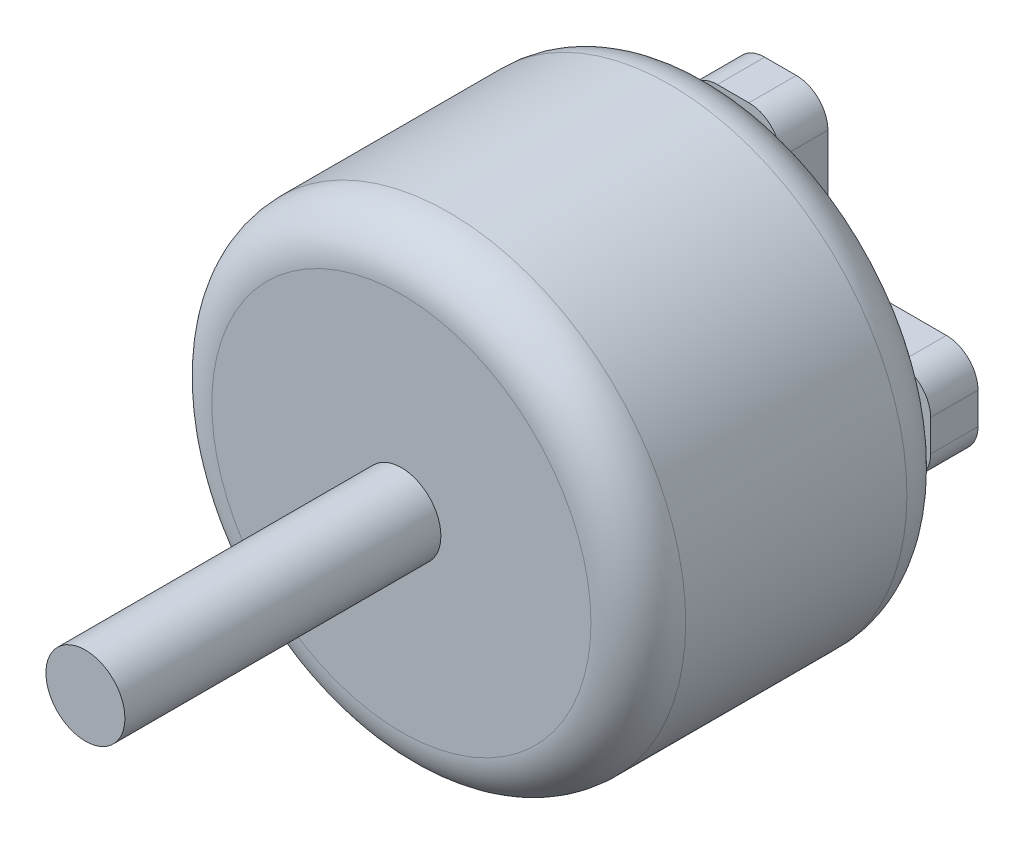
SolidWorks part; units mm, degrees
ref_plane "Front Plane" through (0, 0, 0) normal (0, 0, 1) x (1, 0, 0)
ref_plane "Top Plane" through (0, 0, 0) normal (0, 1, 0) x (1, 0, 0)
ref_plane "Right Plane" through (0, 0, 0) normal (1, 0, 0) x (0, 0, -1)
sketch "Sketch1" plane through (0, 0, 0) normal (0, 0, 1) x (1, 0, 0)
  line L0 (-71.7817, -74.7817) -> (-67.2817, -74.7817)
  line L1 (-78.7817, -65.2817) -> (-76.7817, -65.2817)
  line L2 (-80.7817, -67.2817) -> (-80.7817, -71.7817)
  line L3 (-78.7817, -90.2817) -> (-76.7817, -90.2817)
  line L4 (-74.7817, -67.2817) -> (-74.7817, -71.7817)
  line L5 (-88.2817, -74.7817) -> (-83.7817, -74.7817)
  line L6 (-90.2817, -76.7817) -> (-90.2817, -78.7817)
  line L7 (-88.2817, -80.7817) -> (-83.7817, -80.7817)
  line L8 (-65.2817, -76.7817) -> (-65.2817, -78.7817)
  line L9 (-80.7817, -83.7817) -> (-80.7817, -88.2817)
  line L10 (-74.7817, -83.7817) -> (-74.7817, -88.2817)
  line L11 (-71.7817, -80.7817) -> (-67.2817, -80.7817)
  circle A0 centre (-87.2817, -77.7817) radius 1.6 construction
  circle A1 centre (-77.7817, -87.2817) radius 1.6 construction
  circle A2 centre (-77.7817, -68.2817) radius 1.6 construction
  circle A3 centre (-68.2817, -77.7817) radius 1.6 construction
  arc A4 (-80.7817, -83.7817) -> (-83.7817, -80.7817) centre (-83.7817, -83.7817) ccw
  arc A5 (-74.7817, -83.7817) -> (-71.7817, -80.7817) centre (-71.7817, -83.7817) cw
  arc A6 (-71.7817, -74.7817) -> (-74.7817, -71.7817) centre (-71.7817, -71.7817) cw
  arc A7 (-83.7817, -74.7817) -> (-80.7817, -71.7817) centre (-83.7817, -71.7817) ccw
  arc A8 (-78.7817, -65.2817) -> (-80.7817, -67.2817) centre (-78.7817, -67.2817) ccw
  arc A9 (-76.7817, -65.2817) -> (-74.7817, -67.2817) centre (-76.7817, -67.2817) cw
  arc A10 (-67.2817, -74.7817) -> (-65.2817, -76.7817) centre (-67.2817, -76.7817) cw
  arc A11 (-67.2817, -80.7817) -> (-65.2817, -78.7817) centre (-67.2817, -78.7817) ccw
  arc A12 (-76.7817, -90.2817) -> (-74.7817, -88.2817) centre (-76.7817, -88.2817) ccw
  arc A13 (-80.7817, -88.2817) -> (-78.7817, -90.2817) centre (-78.7817, -88.2817) ccw
  arc A14 (-90.2817, -78.7817) -> (-88.2817, -80.7817) centre (-88.2817, -78.7817) ccw
  arc A15 (-88.2817, -74.7817) -> (-90.2817, -76.7817) centre (-88.2817, -76.7817) ccw
  circle A16 centre (-77.7817, -68.2817) radius 1.6
  circle A17 centre (-68.2817, -77.7817) radius 1.6
  circle A18 centre (-77.7817, -87.2817) radius 1.6
  circle A19 centre (-87.2817, -77.7817) radius 1.6
  point P24 (-74.7817, -80.7817)
  point P39 (-74.7817, -90.2817)
  point P42 (-80.7817, -90.2817)
  point P45 (-90.2817, -80.7817)
  point P48 (-90.2817, -74.7817)
  dimension "D1" = 3
  dimension "D9" = 3
  dimension "D10" = 2
  dimension "D2" = 6
  dimension "D3" = 6
  dimension "D4" = 3
  dimension "D5" = 3
  dimension "D6" = 3
  dimension "D7" = 3
  dimension "D8" = 3
extrude "Boss-Extrude1" add sketch "Sketch1" along normal blind 3
sketch "Sketch2" plane through (0, 0, 3) normal (0, 0, 1) x (1, 0, 0)
  line L0 (-77.7817, -68.2817) -> (-77.7817, -77.7817) construction
  line L1 (-68.2817, -77.7817) -> (-77.7817, -77.7817) construction
  circle A0 centre (-77.7817, -77.7817) radius 2.852
extrude "Boss-Extrude2" add sketch "Sketch2" along normal blind 1
sketch "Sketch3" plane through (0, 0, 4) normal (0, 0, 1) x (1, 0, 0)
  circle A0 centre (-77.7817, -77.7817) radius 15
extrude "Boss-Extrude3" add sketch "Sketch3" along normal blind 20
sketch "Sketch4" plane through (0, 0, 24) normal (0, 0, 1) x (1, 0, 0)
  circle A0 centre (-77.7817, -77.7817) radius 2.5
extrude "Boss-Extrude4" add sketch "Sketch4" along normal blind 20
fillet "Fillet1" radius 3 2 edges at (-62.7817, -77.7817, 24) (-62.7817, -77.7817, 4)
